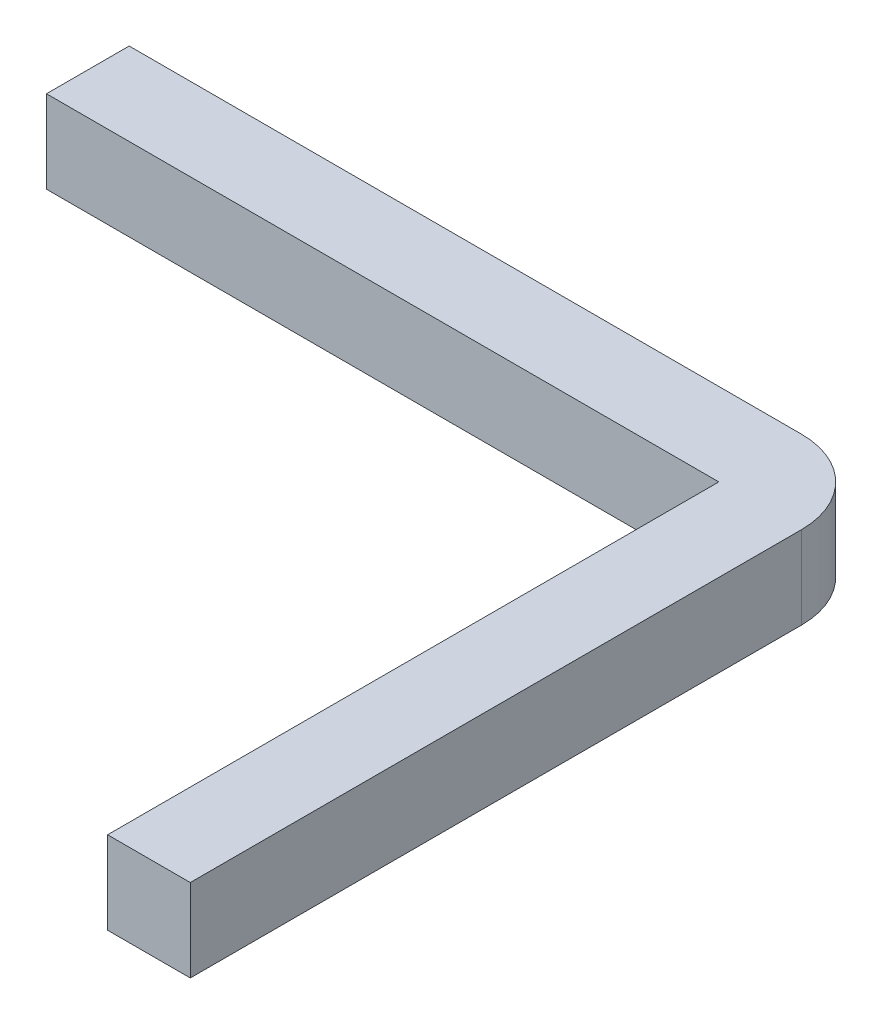
SolidWorks part; units mm, degrees
ref_plane "Alzado" through (0, 0, 0) normal (0, 0, 1) x (1, 0, 0)
ref_plane "Planta" through (0, 0, 0) normal (0, 1, 0) x (1, 0, 0)
ref_plane "Vista lateral" through (0, 0, 0) normal (1, 0, 0) x (0, 0, -1)
sketch "Croquis1" plane through (0, 0, 0) normal (0, 0, 1) x (1, 0, 0)
  line L1 (-105, 11.5) -> (105, 11.5)
  line L2 (-105, 11.5) -> (-105, -11.5)
  line L3 (-105, -11.5) -> (105, -11.5)
  line L4 (105, 11.5) -> (105, -11.5)
  line L5 (-105, 11.5) -> (105, -11.5) construction
  line L6 (-105, -11.5) -> (105, 11.5) construction
  point P0 (0, 0)
  dimension "D1" = 210
  dimension "D2" = 23
extrude "Saliente-Extruir2" add sketch "Croquis1" along normal blind 23
fillet "Redondeo4" radius 23 1 edges at (105, 0, 0) type face fillet first side face at (0, 0, 0) second side face at (105, 0, 11.5)
sketch "Croquis2" plane through (0, 0, 23) normal (0, 0, 1) x (1, 0, 0)
  line L1 (82, -11.5) -> (105, -11.5)
  line L2 (82, -11.5) -> (82, 11.5)
  line L3 (82, 11.5) -> (105, 11.5)
  line L4 (105, -11.5) -> (105, 11.5)
  dimension "D1" = 23
  dimension "D2" = 23
extrude "Saliente-Extruir3" add sketch "Croquis2" along normal blind 170
sketch "Croquis8" plane through (-105, 0, 0) normal (-1, 0, 0) x (0, 0, 1)
  line L1 (1.9359, -9.5) -> (20.9359, -9.5)
  line L2 (1.9359, -9.5) -> (1.9359, 9.5)
  line L3 (1.9359, 9.5) -> (20.9359, 9.5)
  line L4 (20.9359, -9.5) -> (20.9359, 9.5)
  line L5 (1.9359, -9.5) -> (20.9359, 9.5) construction
  line L6 (1.9359, 9.5) -> (20.9359, -9.5) construction
  point P0 (11.4359, 0)
  point P5 (11.4359, 0)
  dimension "D1" = 19
  dimension "D2" = 19
extrude "Cortar-Extruir2" cut sketch "Croquis8" against normal blind 80
